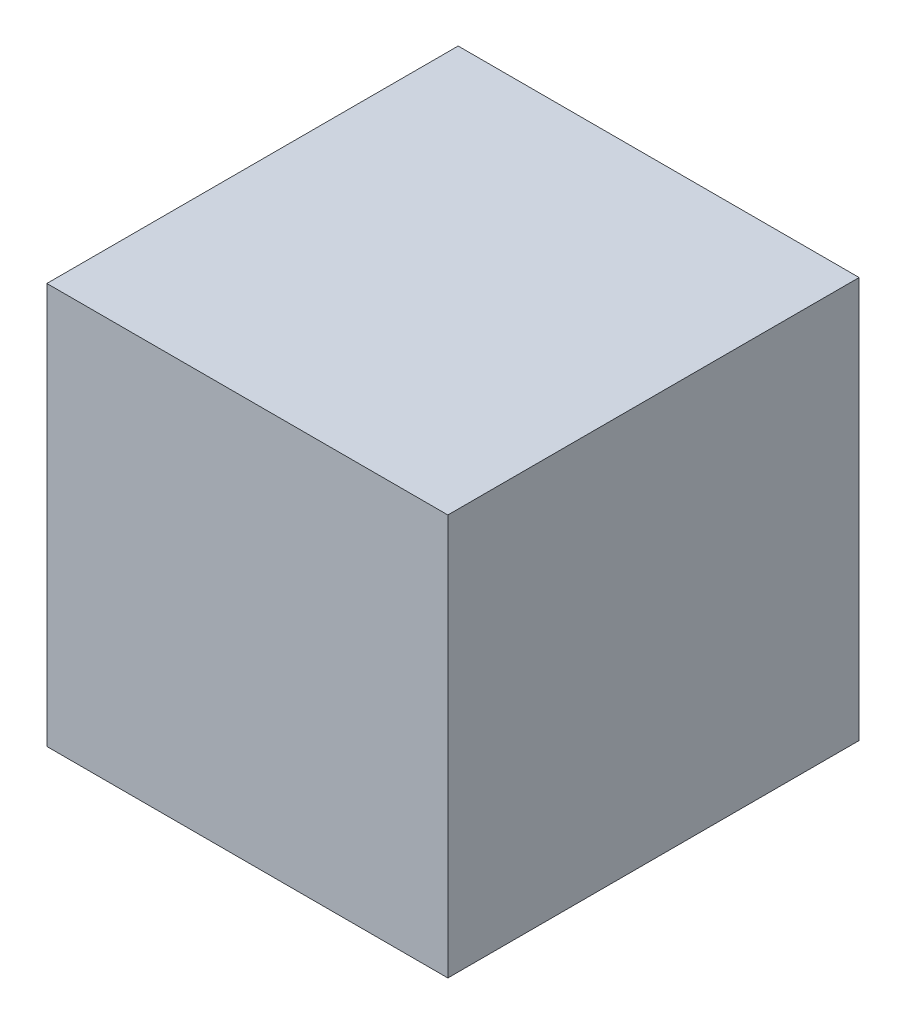
SolidWorks part; units mm, degrees
ref_plane "Ön Düzlem" through (0, 0, 0) normal (0, 0, 1) x (1, 0, 0)
ref_plane "Üst Düzlem" through (0, 0, 0) normal (0, 1, 0) x (1, 0, 0)
ref_plane "Sağ Düzlem" through (0, 0, 0) normal (1, 0, 0) x (0, 0, -1)
sketch "Çizim1" plane through (0, 0, 0) normal (0, 0, 1) x (1, 0, 0)
  line L1 (-4.953, 4.953) -> (4.953, 4.953)
  line L2 (-4.953, 4.953) -> (-4.953, -4.953)
  line L3 (-4.953, -4.953) -> (4.953, -4.953)
  line L4 (4.953, 4.953) -> (4.953, -4.953)
  line L5 (-4.953, 4.953) -> (4.953, -4.953) construction
  line L6 (-4.953, -4.953) -> (4.953, 4.953) construction
  point P0 (0, 0)
  dimension "D1" = 9.906
  dimension "D2" = 9.906
extrude "Yükseklik-Ekstrüzyon1" add sketch "Çizim1" along normal blind 5.08 and the other way blind 5.08
